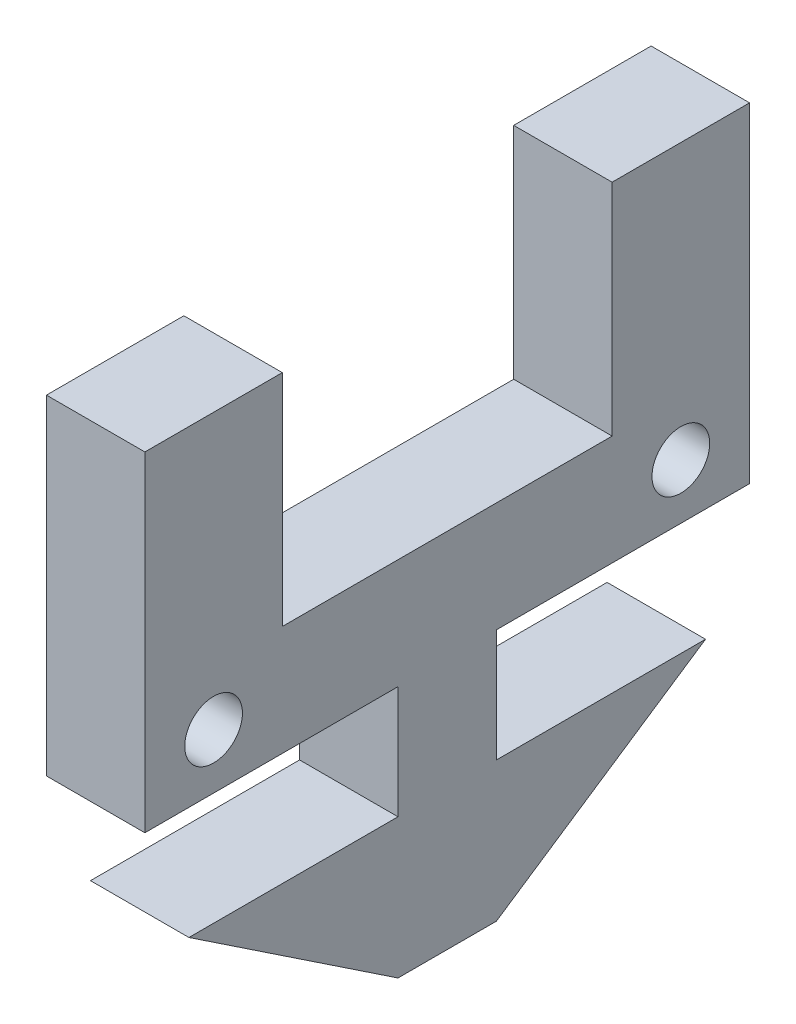
SolidWorks part; units mm, degrees
other "DetailItem2"
ref_plane "Front Plane" through (0, 0, 0) normal (0, 0, 1) x (1, 0, 0)
ref_plane "Top Plane" through (0, 0, 0) normal (0, 1, 0) x (1, 0, 0)
ref_plane "Right Plane" through (0, 0, 0) normal (1, 0, 0) x (0, 0, -1)
sketch "Sketch1" plane through (0, 0, 0) normal (1, 0, 0) x (0, 0, -1)
  line L0 (-6, 6) -> (-6, -2)
  line L1 (-11, -6) -> (11, -6)
  line L2 (-11, -6) -> (-11, 6)
  line L3 (-11, 6) -> (-6, 6)
  line L4 (11, -6) -> (11, 6)
  line L5 (-11, -6) -> (11, 6) construction
  line L6 (-11, 6) -> (11, -6) construction
  line L7 (-6, -2) -> (6, -2)
  line L8 (6, -2) -> (6, 6)
  line L9 (6, 6) -> (11, 6)
  point P0 (0, 0)
  point P8 (0, -2)
  dimension "D1" = 12
  dimension "D2" = 22
  dimension "D3" = 5
  dimension "D4" = 4
extrude "Boss-Extrude1" add sketch "Sketch1" along normal blind 3.5814
sketch "Sketch7" plane through (3.5814, 0, 0) normal (1, 0, 0) x (0, 0, -1)
  line L2 (-6, 6) -> (-11, 6) construction
  line L3 (-8.5, -4) -> (8.5, -4) construction
  circle A0 centre (-8.5, -4) radius 1.05
  circle A1 centre (8.5, -4) radius 1.05
  point P4 (0, -4)
  dimension "D1" = 2.1
  dimension "D2" = 17
  dimension "D3" = 10
extrude "Cut-Extrude5" cut sketch "Sketch7" against normal through all
sketch "Sketch8" plane through (0, 0, 0) normal (1, 0, 0) x (0, 0, -1)
  line L9 (-1.7907, -10.1) -> (-9.398, -10.1)
  line L10 (-1.7907, -6) -> (-1.7907, -10.1)
  line L11 (1.7907, -6) -> (1.7907, -10.1)
  line L12 (-9.398, -10.1) -> (-1.7907, -15.18)
  line L13 (-1.7907, -15.18) -> (1.7907, -15.18)
  line L14 (1.7907, -15.18) -> (9.398, -10.1)
  line L15 (9.398, -10.1) -> (1.7907, -10.1)
  line L16 (-11, -6) -> (11, -6) construction
  line L17 (-1.7907, -6) -> (1.7907, -6)
  point P0 (0, -8.05)
  point P9 (0, -15.18)
  point P10 (1.7907, -8.05)
  dimension "D1" = 3.5814
  dimension "D2" = 4.1
  dimension "D3" = 18.796
  dimension "D4" = 5.08
extrude "Boss-Extrude3" add sketch "Sketch8" along normal up to surface (3.5814 mm away) up to face at (3.5814, -4, 7.45)
